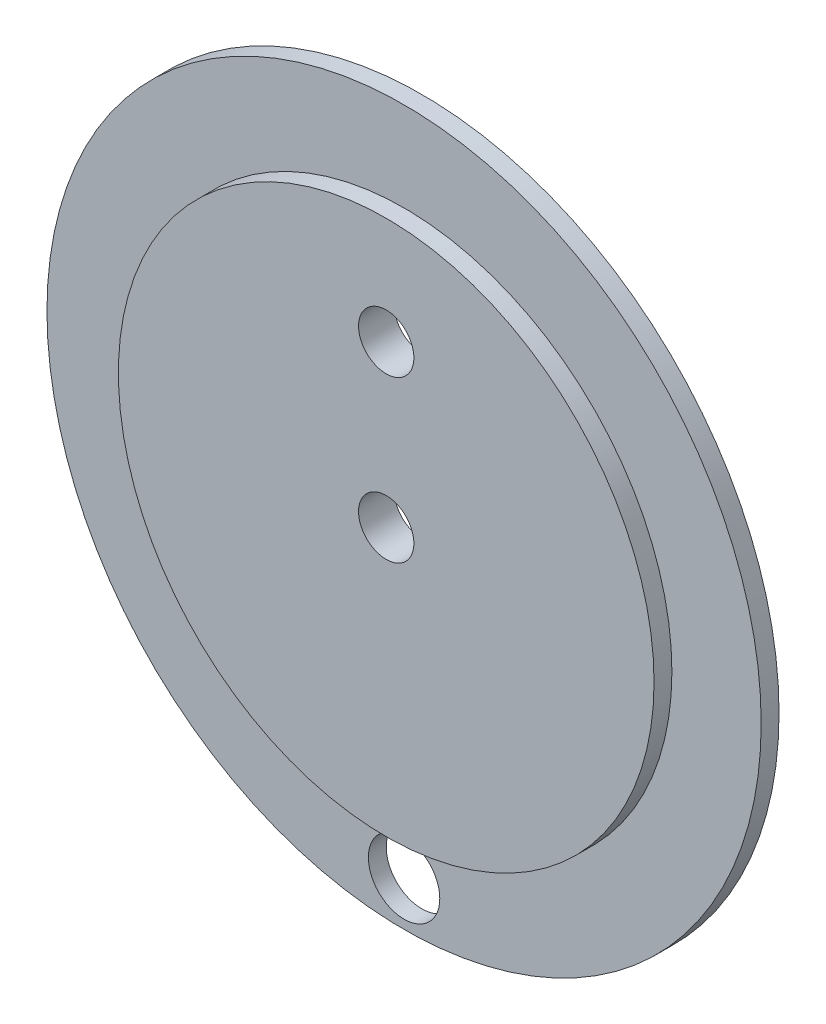
SolidWorks part; units mm, degrees
ref_plane "Front Plane" through (0, 0, 0) normal (1, 0, 0) x (0, 1, 0)
ref_plane "Top Plane" through (0, 0, 0) normal (0, 0, 1) x (0, 1, 0)
ref_plane "Right Plane" through (0, 0, 0) normal (0, 1, 0) x (-1, 0, 0)
sketch "Sketch1" plane through (0, 0, 0) normal (0, 0, 1) x (0, 1, 0)
  line L1 (-15, 0) -> (-20, 0) construction
  circle A0 centre (0, 0) radius 15
  circle A1 centre (0, 0) radius 1.55
  circle A2 centre (9, 0) radius 1.55
  circle A3 centre (0, 0) radius 20
  circle A4 centre (-17.5, 0) radius 2
  point P9 (0, 0)
  dimension "D1" = 30
  dimension "D2" = 3.1
  dimension "D3" = 3.1
  dimension "D5" = 40
  dimension "D6" = 4
  dimension "D4" = 9
extrude "Boss-Extrude1" add sketch "Sketch1" along normal blind 1 contours A3 A0 region at (0, -19.9434, 0)
extrude "Boss-Extrude2" add sketch "Sketch1<4>" along normal blind 2 contours A0 A2 A1 region at (0, -14.5757, 0)
sketch "Sketch1<4>" plane through (0, 0, 0) normal (0, 0, 1) x (0, 1, 0) same geometry as "Sketch1"
